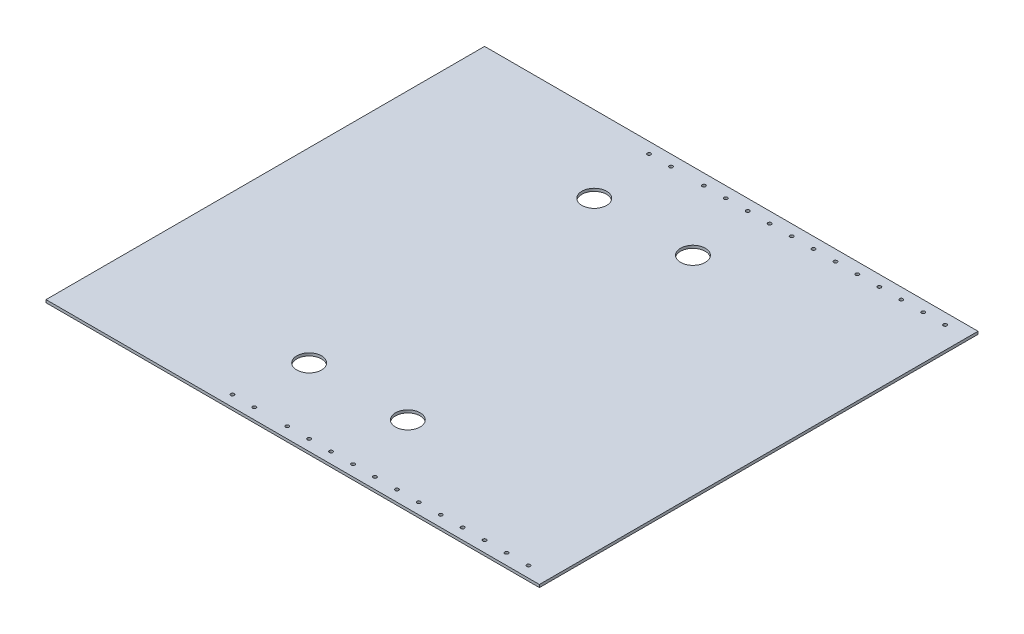
SolidWorks part; units mm, degrees
ref_plane "Front Plane" through (0, 0, 0) normal (0, 0, 1) x (1, 0, 0)
ref_plane "Top Plane" through (0, 0, 0) normal (0, 1, 0) x (1, 0, 0)
ref_plane "Right Plane" through (0, 0, 0) normal (1, 0, 0) x (0, 0, -1)
sketch "Sketch1" plane through (0, 0, 0) normal (0, 1, 0) x (1, 0, 0)
  line L1 (0, 0) -> (571.5, 0)
  line L2 (0, 0) -> (0, 508)
  line L3 (0, 508) -> (571.5, 508)
  line L4 (571.5, 0) -> (571.5, 508)
  dimension "D1" = 571.5
  dimension "D2" = 508
extrude "Boss-Extrude1" add sketch "Sketch1" along normal blind 3.175
sketch "Sketch2" plane through (0, 3.175, 0) normal (0, 1, 0) x (1, 0, 0)
  line L0 (273.05, 419.1) -> (273.05, 508) construction
  line L1 (215.9, 419.1) -> (330.2, 419.1) construction
  line L3 (215.9, 88.9) -> (330.2, 88.9) construction
  line L4 (571.5, 0) -> (571.5, 508) construction
  line L5 (571.5, 508) -> (0, 508) construction
  line L6 (273.05, 88.9) -> (273.05, 0) construction
  line L7 (0, 0) -> (571.5, 0) construction
  circle A0 centre (215.9, 419.1) radius 14.2875
  circle A1 centre (330.2, 419.1) radius 14.2875
  circle A2 centre (215.9, 88.9) radius 14.2875
  circle A3 centre (330.2, 88.9) radius 14.2875
  dimension "D1" = 28.575
  dimension "D2" = 28.575
  dimension "D3" = 28.575
  dimension "D4" = 28.575
  dimension "D5" = 114.3
  dimension "D6" = 114.3
  dimension "D7" = 330.2
  dimension "D8" = 241.3
extrude "Cut-Extrude1" cut sketch "Sketch2" against normal blind 3.175
sketch "Sketch4" plane through (0, 3.175, 0) normal (0, 1, 0) x (1, 0, 0)
  line L0 (571.5, 495.3) -> (0, 495.3) construction
  line L1 (571.5, 0) -> (571.5, 508) construction
  line L2 (0, 508) -> (0, 0) construction
  line L3 (571.5, 508) -> (0, 508) construction
  line L4 (0, 254) -> (571.5, 254) construction
  line L5 (571.5, 12.7) -> (0, 12.7) construction
  circle A0 centre (546.1, 495.3) radius 2.0193
  circle A1 centre (520.7, 495.3) radius 2.0193
  circle A2 centre (495.3, 495.3) radius 2.0193
  circle A3 centre (469.9, 495.3) radius 2.0193
  circle A4 centre (444.5, 495.3) radius 2.0193
  circle A5 centre (419.1, 495.3) radius 2.0193
  circle A6 centre (393.7, 495.3) radius 2.0193
  circle A7 centre (368.3, 495.3) radius 2.0193
  circle A8 centre (342.9, 495.3) radius 2.0193
  circle A9 centre (317.5, 495.3) radius 2.0193
  circle A10 centre (292.1, 495.3) radius 2.0193
  circle A11 centre (266.7, 495.3) radius 2.0193
  circle A12 centre (228.6, 495.3) radius 2.0193
  circle A13 centre (203.2, 495.3) radius 2.0193
  circle A14 centre (203.2, 12.7) radius 2.0193
  circle A15 centre (228.6, 12.7) radius 2.0193
  circle A16 centre (266.7, 12.7) radius 2.0193
  circle A17 centre (292.1, 12.7) radius 2.0193
  circle A18 centre (317.5, 12.7) radius 2.0193
  circle A19 centre (342.9, 12.7) radius 2.0193
  circle A20 centre (368.3, 12.7) radius 2.0193
  circle A21 centre (393.7, 12.7) radius 2.0193
  circle A22 centre (419.1, 12.7) radius 2.0193
  circle A23 centre (444.5, 12.7) radius 2.0193
  circle A24 centre (469.9, 12.7) radius 2.0193
  circle A25 centre (495.3, 12.7) radius 2.0193
  circle A26 centre (520.7, 12.7) radius 2.0193
  circle A27 centre (546.1, 12.7) radius 2.0193
  dimension "D2" = 4.0386
  dimension "D3" = 25.4
  dimension "D5" = 38.1
  dimension "D6" = 25.4
  dimension "D1" = 12.7
  dimension "D4" = 12
extrude "Cut-Extrude3" cut sketch "Sketch4" against normal through all both
